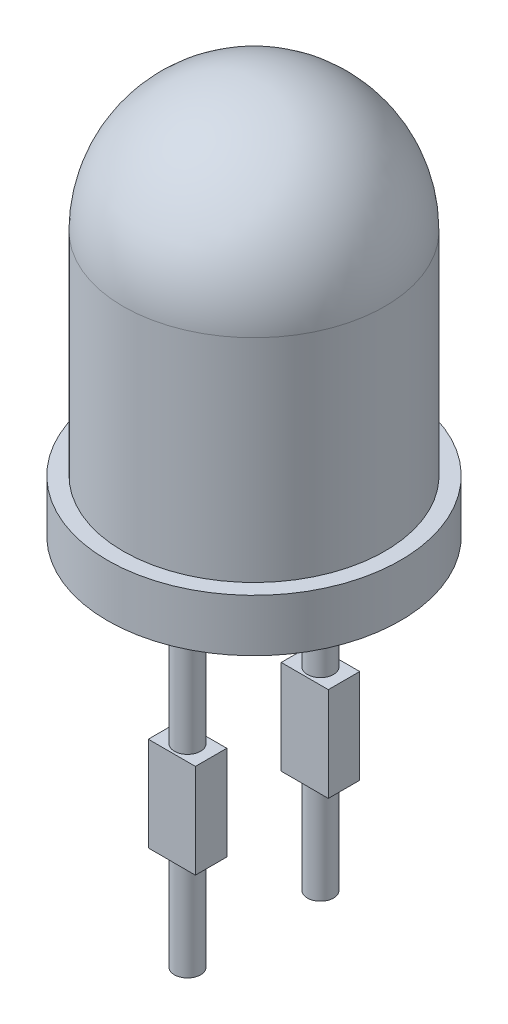
SolidWorks part; units mm, degrees
ref_plane "Front Plane" through (0, 0, 0) normal (0, 0, 1) x (1, 0, 0)
ref_plane "Top Plane" through (0, 0, 0) normal (0, 1, 0) x (1, 0, 0)
ref_plane "Right Plane" through (0, 0, 0) normal (1, 0, 0) x (0, 0, -1)
sketch "Sketch1" plane through (0, 0, 0) normal (1, 0, 0) x (0, 0, -1)
  line L0 (0, 4.525) -> (0, -10.9525) construction
  line L1 (-2.5, 2.025) -> (-2.5, -2.025)
  line L2 (-2.5, -2.025) -> (-2.8, -2.025)
  line L3 (-2.8, -2.025) -> (-2.8, -3.025)
  line L4 (-2.8, -3.025) -> (0, -3.025)
  line L5 (0, 4.525) -> (-4.2269, 4.525) construction
  line L6 (0, 4.525) -> (0, -3.025)
  arc A0 (-2.5, 2.025) -> (0, 4.525) centre (0, 2.025) cw
  point P11 (-2.5, 0)
  dimension "D1" = 5
  dimension "D2" = 7.55
  dimension "D3" = 1
  dimension "D4" = 5.6
revolve "Revolve1" add sketch "Sketch1" angle 360 about L0
sketch "Sketch2" plane through (0, -3.025, 0) normal (0, -1, 0) x (1, 0, 0)
  line L0 (0, 0) -> (3.908, 0) construction
  circle A0 centre (0, 1.27) radius 0.25
  circle A1 centre (0, -1.27) radius 0.25
  dimension "D1" = 2.54
  dimension "D2" = 0.5
extrude "Boss-Extrude1" add sketch "Sketch2" along normal blind 11 separate body
sketch "Sketch3" plane through (0, 0, 0) normal (1, 0, 0) x (0, 0, -1)
  line L0 (1.27, -3.025) -> (1.27, -15.6133) construction
  line L1 (0.97, -5.825) -> (1.57, -5.825)
  line L2 (0.97, -5.825) -> (0.97, -7.625)
  line L3 (0.97, -7.625) -> (1.57, -7.625)
  line L4 (1.57, -5.825) -> (1.57, -7.625)
  line L5 (0.97, -5.825) -> (1.57, -7.625) construction
  line L6 (0.97, -7.625) -> (1.57, -5.825) construction
  line L7 (1.52, -3.025) -> (1.02, -3.025) construction
  line L8 (-2.8, -3.025) -> (2.8, -3.025) construction
  line L9 (0, 0) -> (0, -3.6509) construction
  line L10 (-0.97, -7.625) -> (-1.57, -7.625)
  line L11 (-1.57, -5.825) -> (-1.57, -7.625)
  line L12 (-0.97, -5.825) -> (-1.57, -5.825)
  line L13 (-0.97, -5.825) -> (-0.97, -7.625)
  point P0 (1.27, -6.725)
  dimension "D1" = 0.6
  dimension "D2" = 2.8
  dimension "D3" = 1.8
extrude "Boss-Extrude2" add sketch "Sketch3" along normal mid plane 0.9
sketch "Sketch4" plane through (0, 0, 0) normal (1, 0, 0) x (0, 0, -1)
  line L0 (-2.8, -3.025) -> (2.8, -3.025) construction
  line L1 (-4.3846, -9.525) -> (3.9451, -9.525)
  line L2 (-4.3846, -9.525) -> (-4.3846, -15.9711)
  line L3 (-4.3846, -15.9711) -> (3.9451, -15.9711)
  line L4 (3.9451, -9.525) -> (3.9451, -15.9711)
  dimension "D1" = 6.5
extrude "Cut-Extrude1" cut sketch "Sketch4" against normal through all both and the other way through all
